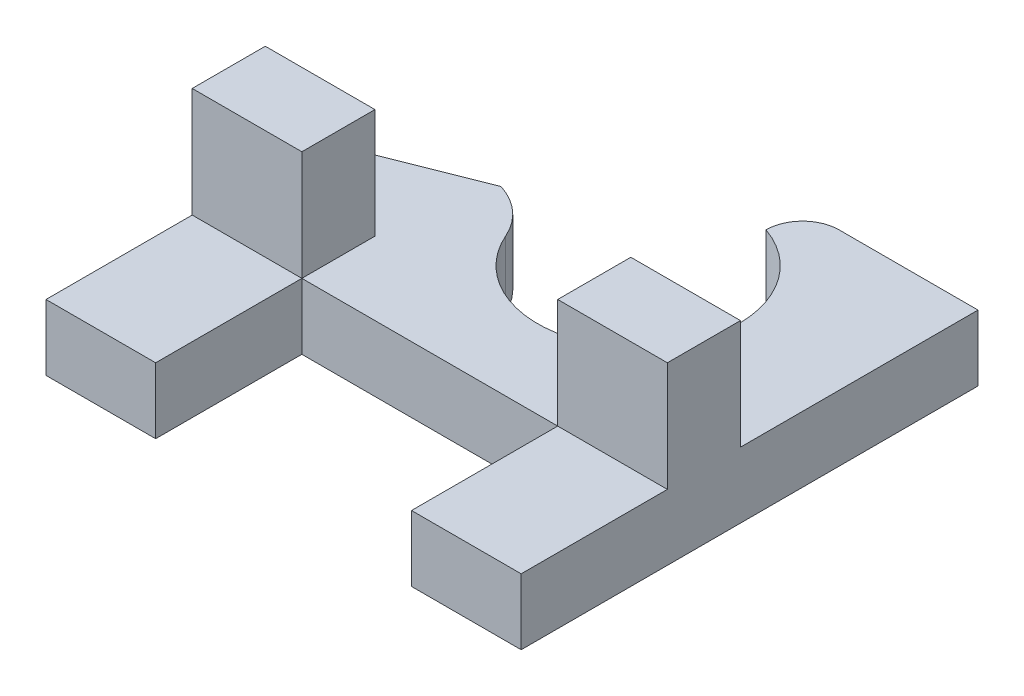
SolidWorks part; units mm, degrees
ref_plane "Front Plane" through (0, 0, 0) normal (0, 0, 1) x (1, 0, 0)
ref_plane "Top Plane" through (0, 0, 0) normal (0, 1, 0) x (1, 0, 0)
ref_plane "Right Plane" through (0, 0, 0) normal (1, 0, 0) x (0, 0, -1)
sketch "Sketch1" plane through (0, 0, 0) normal (0, 1, 0) x (1, 0, 0)
  line L0 (6.5, 2.5) -> (6.5, 0)
  line L1 (3.5, 0) -> (-3.5, 0)
  line L2 (-6.5, 0) -> (-6.5, 2.5)
  line L5 (-6.5, 2.5) -> (-6.5, 3.5)
  line L7 (6.5, 0) -> (6.5, -4)
  line L8 (6.5, -4) -> (3.5, -4)
  line L9 (3.5, 0) -> (3.5, -4)
  line L11 (-6.5, 0) -> (-6.5, -4)
  line L12 (-6.5, -4) -> (-3.5, -4)
  line L13 (-3.5, 0) -> (-3.5, -4)
  line L15 (6.5, 4.9) -> (6.5, 2.5)
  line L17 (-1.95, 4.9) -> (-2.95, 4.9)
  line L18 (-2.95, 4.9) -> (-6.5, 3.5)
  line L19 (1.7, 7.4986) -> (1.7, 8.4986)
  line L20 (1.7, 8.4986) -> (6.5, 8.4986)
  line L21 (6.5, 8.4986) -> (6.5, 4.9)
  arc A2 (-1.95, 4.9) -> (3.3581, 3.8908) centre (0.8, 4.9) ccw
  arc A3 (3.3581, 3.8908) -> (1.7, 7.4986) centre (0.8, 4.9) ccw
  point P0 (0, 0)
  dimension "D1" = 2.4
  dimension "D2" = 5.5
  dimension "D3" = 13
  dimension "D4" = 7.3
  dimension "D5" = 2.5
  dimension "D6" = 1
  dimension "D7" = 1
  dimension "D8" = 4
  dimension "D9" = 3
  dimension "D10" = 3.3
  dimension "D11" = 2.4
  dimension "D12" = 1
  dimension "D13" = 4.8
extrude "Boss-Extrude1" add sketch "Sketch1" along normal blind 1.8
fillet "Fillet1" radius 2 1 edges at (-1.95, 0.9, -4.9)
fillet "Fillet3" radius 1 1 edges at (1.7, 0.9, -8.4986)
ref_plane "Plane1" through (0, 1.8, 0) normal (0, 1, 0) x (1, 0, 0)
sketch "Sketch2" plane through (0, 1.8, 0) normal (0, 1, 0) x (1, 0, 0)
  line L0 (-6.5, 3.5) -> (-6.5, -4) construction
  line L1 (-3.5, 0) -> (-6.5, 0)
  line L2 (-3.5, 0) -> (-3.5, 2)
  line L3 (-3.5, 2) -> (-6.5, 2)
  line L4 (-6.5, 0) -> (-6.5, 2)
  line L5 (6.5, -4) -> (6.5, 8.4986) construction
  line L6 (3.5, 0) -> (6.5, 0)
  line L7 (3.5, 0) -> (3.5, 2)
  line L8 (3.5, 2) -> (6.5, 2)
  line L9 (6.5, 0) -> (6.5, 2)
  dimension "D1" = 2
extrude "Boss-Extrude2" add sketch "Sketch2" along normal blind 3
